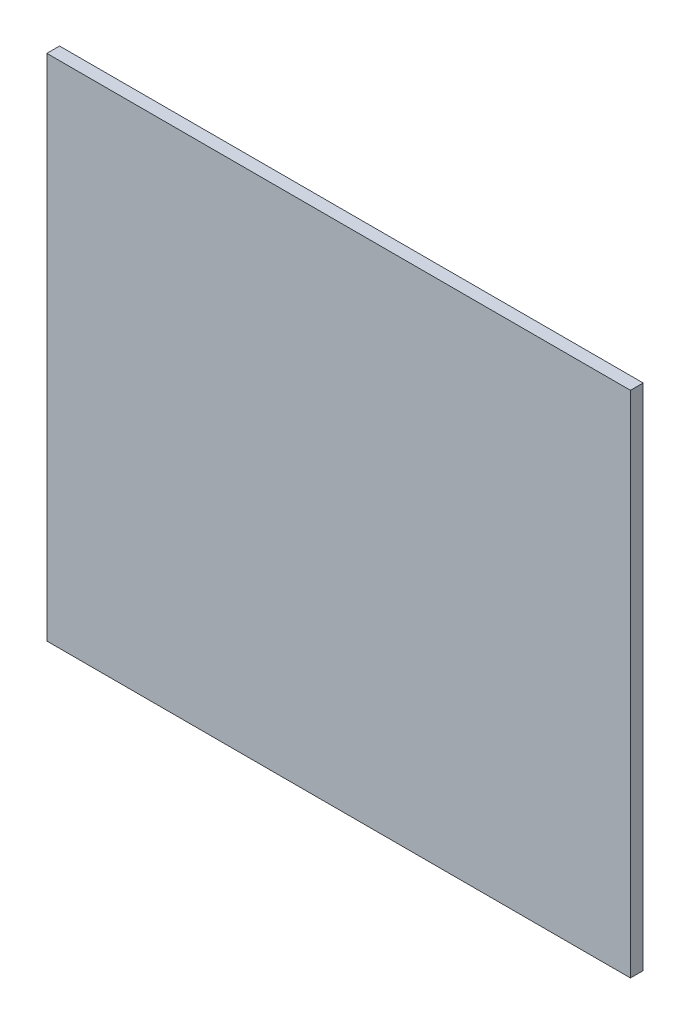
SolidWorks part; units mm, degrees
material "Pine"
ref_plane "Front Plane" through (0, 0, 0) normal (0, 0, 1) x (1, 0, 0)
ref_plane "Top Plane" through (0, 0, 0) normal (0, 1, 0) x (1, 0, 0)
ref_plane "Right Plane" through (0, 0, 0) normal (1, 0, 0) x (0, 0, -1)
sketch "Sketch2" plane through (0, 0, 0) normal (0, 0, 1) x (1, 0, 0)
  line L1 (-211.4484, 257.8858) -> (334.6516, 257.8858)
  line L2 (-211.4484, 257.8858) -> (-211.4484, -218.3642)
  line L3 (-211.4484, -218.3642) -> (334.6516, -218.3642)
  line L4 (334.6516, 257.8858) -> (334.6516, -218.3642)
  dimension "D1" = 546.1
  dimension "D2" = 476.25
extrude "Boss-Extrude1" add sketch "Sketch2" along normal blind 11.9062
